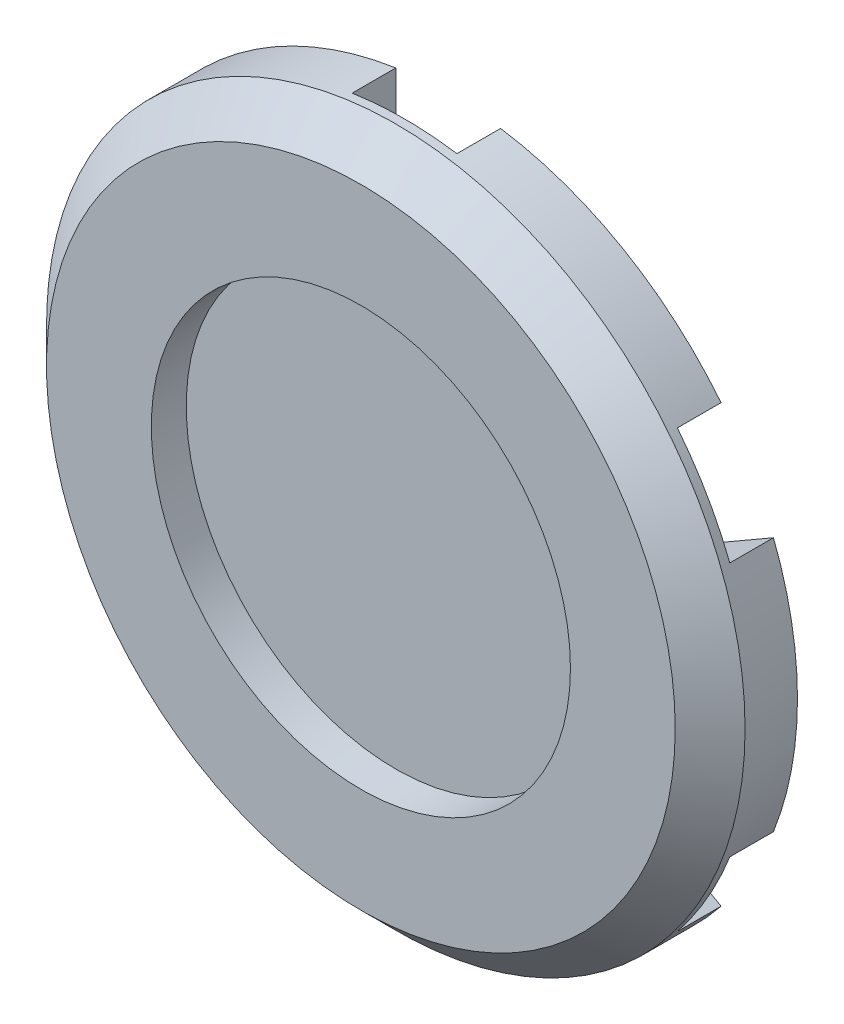
SolidWorks part; units mm, degrees
ref_plane "Front Plane" through (0, 0, 0) normal (1, 0, 0) x (0, 1, 0)
ref_plane "Top Plane" through (0, 0, 0) normal (0, 0, 1) x (0, 1, 0)
ref_plane "Right Plane" through (0, 0, 0) normal (0, 1, 0) x (-1, 0, 0)
sketch "Sketch1" plane through (0, 0, 0) normal (0, 0, 1) x (0, 1, 0)
  circle A0 centre (0, 0) radius 60
  circle A1 centre (0, 0) radius 100
  dimension "D1" = 120
  dimension "D2" = 200
extrude "Boss-Extrude1" add sketch "Sketch1" along normal blind 25 contours A0 | A1 A0 region at (0, 0, 0) region at (0, -97.1716, 0)
extrude "Cut-Extrude1" cut sketch "Sketch1<3>" against normal blind 10 from surface contours A0 region at (0, 0, 0) starting at face at (100, 0, 25)
sketch "Sketch1<3>" plane through (0, 0, 0) normal (0, 0, 1) x (0, 1, 0) same geometry as "Sketch1"
chamfer "Chamfer1" distance 10 angle 45 1 edges at (100, 0, 25)
sketch "Sketch3" plane through (0, 0, 0) normal (0, 0, -1) x (1, 0, 0)
  line L0 (0, 0) -> (0, 100) construction
  line L3 (-15, 98.8686) -> (-15, 68.8686)
  line L4 (-15, 68.8686) -> (15, 68.8686)
  line L5 (15, 98.8686) -> (15, 68.8686)
  circle A0 centre (0, 0) radius 100 construction
  arc A1 (15, 98.8686) -> (-15, 98.8686) centre (0, 0) ccw
  point P10 (0, 68.8686)
  point P11 (0, 0)
  dimension "D1" = 30
  dimension "D2" = 30
extrude "Cut-Extrude2" cut sketch "Sketch3" against normal blind 12.5
pattern_circular "CirPattern1" count 6 over 360 about axis through (0, 0, 0) along (0, 0, 1) of "Cut-Extrude2"
